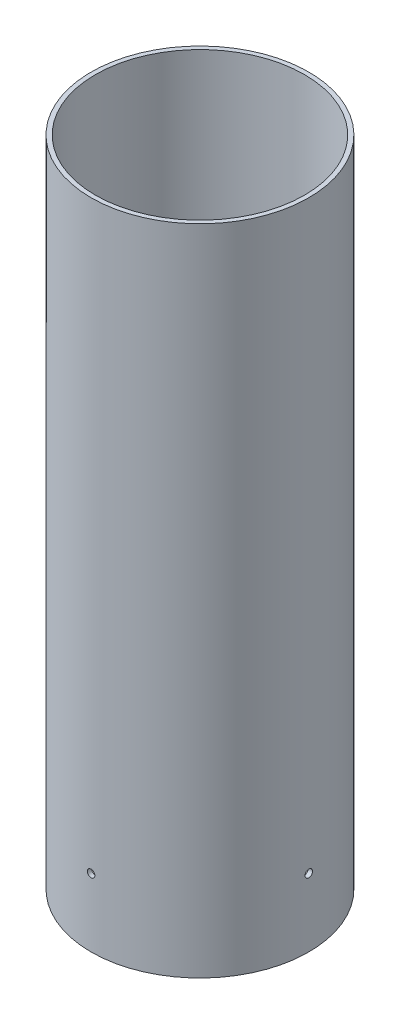
SolidWorks part; units mm, degrees
ref_plane "Front Plane" through (0, 0, 0) normal (0, 0, 1) x (1, 0, 0)
ref_plane "Top Plane" through (0, 0, 0) normal (0, 1, 0) x (1, 0, 0)
ref_plane "Right Plane" through (0, 0, 0) normal (1, 0, 0) x (0, 0, -1)
sketch "Sketch2" plane through (0, 0, 0) normal (0, 1, 0) x (1, 0, 0)
  circle A0 centre (0, 0) radius 50.8
  circle A1 centre (0, 0) radius 48.768
  dimension "D1" = 101.6
  dimension "D2" = 97.536
extrude "Coupler Extrusion" add sketch "Sketch2" along normal blind 304.8
ref_plane "Plane1" through (0, 0, 50.8) normal (0, 0, 1) x (1, 0, 0)
sketch "Sketch3" plane through (0, 0, 50.8) normal (0, 0, 1) x (1, 0, 0)
  line L0 (0, 304.8) -> (0, 0) construction
  line L1 (48.768, 304.8) -> (-48.768, 304.8) construction
  line L2 (-48.768, 0) -> (48.768, 0) construction
  circle A0 centre (0, 31.75) radius 1.7526
  dimension "D1" = 31.75
  dimension "D2" = 3.5052
extrude "Bulkhead Holes" cut sketch "Sketch3" against normal up to next
pattern_circular "CirPattern1" count 4 over 360 about axis through (0, 304.8, 0) along (0, -1, 0) of "Bulkhead Holes"
